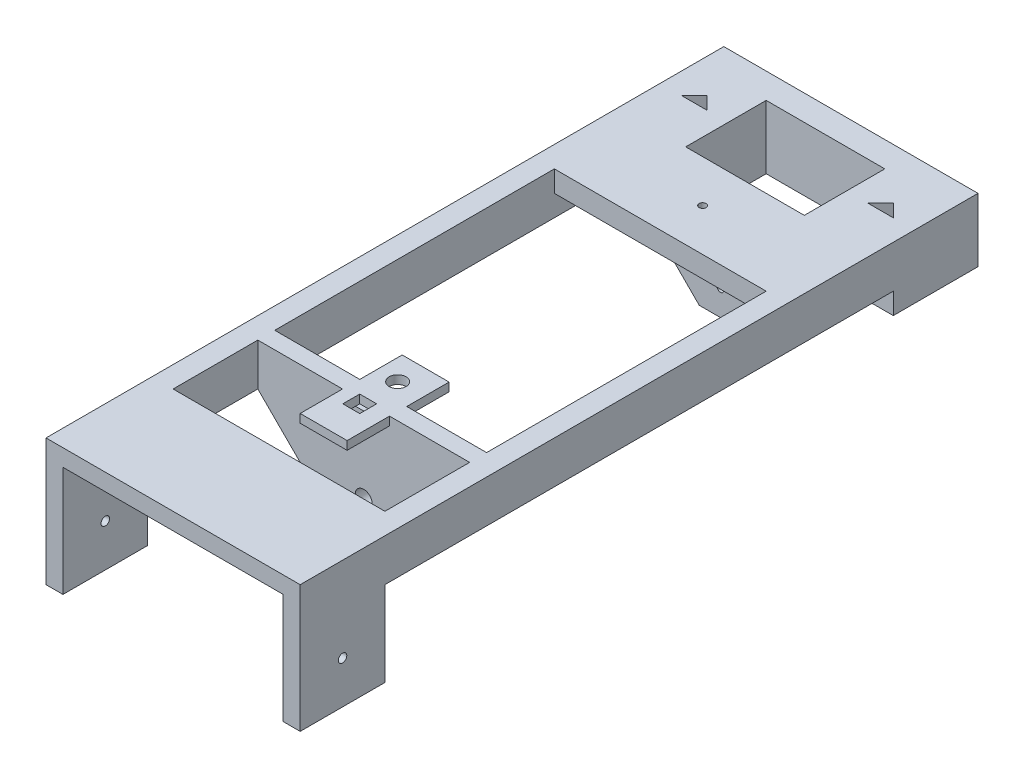
SolidWorks part; units mm, degrees
other "Markup1"
sketch "Sketch19" plane through (-15, 15, -40) normal (-0.0389, 0.0826, -0.9958) x (-0.519, -0.8533, -0.0505)
material "Alumina"
ref_plane "Front Plane" through (0, 0, 0) normal (0, 0, 1) x (1, 0, 0)
ref_plane "Top Plane" through (0, 0, 0) normal (0, 1, 0) x (1, 0, 0)
ref_plane "Right Plane" through (0, 0, 0) normal (1, 0, 0) x (0, 0, -1)
sketch "Sketch1" plane through (0, 0, 0) normal (0, 1, 0) x (1, 0, 0)
  line L1 (-15, 40) -> (15, 40)
  line L2 (-15, 40) -> (-15, -40)
  line L3 (-15, -40) -> (15, -40)
  line L4 (15, 40) -> (15, -40)
  line L5 (-15, 40) -> (15, -40) construction
  line L6 (-15, -40) -> (15, 40) construction
  point P0 (0, 0)
  dimension "D1" = 30
  dimension "D2" = 80
extrude "Boss-Extrude1" add sketch "Sketch1" along normal blind 5
sketch "Sketch2" plane through (15, 0, 0) normal (1, 0, 0) x (0, 0, -1)
  line L1 (-40, 0) -> (-30, 0)
  line L2 (-40, 0) -> (-40, -10)
  line L3 (-40, -10) -> (-30, -10)
  line L4 (-30, 0) -> (-30, -10)
  line L5 (40, 0) -> (30, 0)
  line L6 (40, 0) -> (40, -10)
  line L7 (40, -10) -> (30, -10)
  line L8 (30, 0) -> (30, -10)
  dimension "D1" = 10
  dimension "D2" = 10
  dimension "D3" = 10
  dimension "D4" = 10
extrude "Boss-Extrude2" add sketch "Sketch2" against normal blind 30
sketch "Sketch3" plane through (15, 0, 0) normal (1, 0, 0) x (0, 0, -1)
  line L0 (-40, 5) -> (-40, -10) construction
  line L2 (-40, -10) -> (-30, -10) construction
  line L15 (40, 5) -> (40, -10) construction
  line L16 (30, -10) -> (40, -10)
  line L17 (30, -10) -> (30, -2.5)
  line L18 (30, -2.5) -> (40, -2.5)
  line L19 (40, -10) -> (40, -2.5)
  circle A0 centre (-35, -5) radius 0.5
  dimension "D1" = 1
  dimension "D2" = 7.5
  dimension "D3" = 5
  dimension "D4" = 5
extrude "Cut-Extrude1" cut sketch "Sketch3" against normal through all both and the other way through all
sketch "Sketch4" plane through (0, 5, 0) normal (0, 1, 0) x (1, 0, 0)
  line L9 (-12.5, -27.5) -> (12.5, -27.5)
  line L10 (-12.5, -27.5) -> (-12.5, 27.5)
  line L11 (-12.5, 27.5) -> (12.5, 27.5)
  line L12 (12.5, -27.5) -> (12.5, 27.5)
  line L13 (-12.5, -27.5) -> (12.5, 27.5) construction
  line L14 (-12.5, 27.5) -> (12.5, -27.5) construction
  point P0 (0, 0)
  dimension "D1" = 55
  dimension "D2" = 25
extrude "Cut-Extrude2" cut sketch "Sketch4" against normal through all both and the other way through all
sketch "Sketch20" plane through (0, 5, 0) normal (0, 1, 0) x (1, 0, 0)
  line L0 (11, 34) -> (9.5, 32.5)
  line L1 (11, 34) -> (12.5, 32.5)
  line L2 (9.5, 32.5) -> (12.5, 32.5)
  line L3 (-11, 34) -> (-12.5, 32.5)
  line L4 (-11, 34) -> (-9.5, 32.5)
  line L5 (-12.5, 32.5) -> (-9.5, 32.5)
  line L6 (-15, 40) -> (-15, -40) construction
  line L7 (15, -40) -> (15, 40) construction
  line L9 (12.5, 27.5) -> (-12.5, 27.5) construction
  dimension "D1" = 3
  dimension "D2" = 3
  dimension "D3" = 5
  dimension "D4" = 5
  dimension "D5" = 2.5
  dimension "D6" = 2.5
extrude "Cut-Extrude4" cut sketch "Sketch20" against normal through all both and the other way through all
sketch "Sketch22" plane through (0, 0, 40) normal (0, 0, 1) x (1, 0, 0)
  line L0 (-15, -10) -> (15, -10) construction
  line L1 (-13, -10) -> (13, -10)
  line L2 (-13, -10) -> (-13, 3)
  line L3 (-13, 3) -> (13, 3)
  line L4 (13, -10) -> (13, 3)
  line L5 (-15, 5) -> (15, 5) construction
  line L6 (-15, 5) -> (-15, -10) construction
  line L7 (15, 5) -> (15, -10) construction
  dimension "D1" = 2
  dimension "D2" = 2
  dimension "D3" = 2
extrude "Cut-Extrude6" cut sketch "Sketch22" against normal up to surface (10 mm away) up to face at (0, -5, 30)
sketch "Sketch23" plane through (0, 5, 0) normal (0, 1, 0) x (1, 0, 0)
  line L0 (-12.5, 27.5) -> (-12.5, -27.5) construction
  line L5 (12.5, -27.5) -> (12.5, 27.5) construction
  line L7 (-12.5, -17.5) -> (12.5, -17.5)
  line L8 (-12.5, -17.5) -> (-12.5, -15.5)
  line L9 (-12.5, -15.5) -> (12.5, -15.5)
  line L10 (12.5, -17.5) -> (12.5, -15.5)
  line L11 (-12.5, -27.5) -> (12.5, -27.5) construction
  dimension "D1" = 2
  dimension "D4" = 10
extrude "Boss-Extrude3" add sketch "Sketch23" against normal blind 15
sketch "Sketch24" plane through (0, 0, 17.5) normal (0, 0, 1) x (1, 0, 0)
  line L0 (-12.5, -10) -> (12.5, -10) construction
  line L1 (-12.5, -10) -> (-12.5, 0) construction
  circle A0 centre (0, -5) radius 1
  dimension "D1" = 2
  dimension "D2" = 5
  dimension "D3" = 12.5
extrude "Cut-Extrude7" cut sketch "Sketch24" against normal up to surface (2 mm away) contours A0 up to face at (0, -1.6667, 15.5)
chamfer "Chamfer1" distance 10 angle 45 2 edges at (-12.5, -10, 16.5) (12.5, -10, 16.5)
sketch "Sketch25" plane through (0, 5, 0) normal (0, 1, 0) x (1, 0, 0)
  line L0 (3.0765, -15.5) -> (-2.4635, -15.5)
  line L7 (-2.4635, -15.5) -> (-2.4635, -10.5)
  line L8 (-2.4635, -10.5) -> (3.0765, -10.5)
  line L9 (3.0765, -15.5) -> (3.0765, -10.5)
  line L10 (-2.4635, -15.5) -> (3.0765, -10.5) construction
  line L11 (-2.4635, -10.5) -> (3.0765, -15.5) construction
  line L12 (-2.5, -17.5) -> (3.04, -17.5)
  line L13 (-2.5, -17.5) -> (-2.5, -22.5)
  line L14 (-2.5, -22.5) -> (3.04, -22.5)
  line L15 (3.04, -17.5) -> (3.04, -22.5)
  point P0 (0, 0)
  point P1 (0.3065, -13)
  dimension "D1" = 5
  dimension "D2" = 5.54
  dimension "D3" = 5.54
  dimension "D4" = 5
extrude "Boss-Extrude4" add sketch "Sketch25" against normal blind 1
sketch "Sketch26" plane through (0, 5, 0) normal (0, 1, 0) x (1, 0, 0)
  line L1 (-2.4635, -15.5) -> (-12.5, -15.5) construction
  circle A0 centre (0, -13.5) radius 1
  dimension "D1" = 2
  dimension "D2" = 2
extrude "Cut-Extrude8" cut sketch "Sketch26" against normal through all both and the other way through all
sketch "Sketch27" plane through (0, 5, 0) normal (0, 1, 0) x (1, 0, 0)
  line L1 (-0.9711, -19) -> (1.0289, -19)
  line L2 (-0.9711, -19) -> (-0.9711, -17)
  line L3 (-0.9711, -17) -> (1.0289, -17)
  line L4 (1.0289, -19) -> (1.0289, -17)
  line L5 (-0.9711, -19) -> (1.0289, -17) construction
  line L6 (-0.9711, -17) -> (1.0289, -19) construction
  circle A0 centre (0, -13.5) radius 1 construction
  point P0 (0.0289, -18)
  dimension "D3" = 4.5
  dimension "D1" = 2
  dimension "D2" = 2
extrude "Cut-Extrude9" cut sketch "Sketch27" against normal blind 1
sketch "Sketch28" plane through (0, 5, 0) normal (0, 1, 0) x (1, 0, 0)
  line L2 (12.5, 27.5) -> (-12.5, 27.5) construction
  line L3 (-7, 27.5) -> (7, 27.5)
  line L4 (-7, 27.5) -> (-7, 37)
  line L5 (-7, 37) -> (7, 37)
  line L6 (7, 27.5) -> (7, 37)
  line L7 (-15, 40) -> (-15, -40) construction
  line L8 (15, -40) -> (15, 40) construction
  line L9 (15, 40) -> (-15, 40) construction
  dimension "D1" = 8
  dimension "D2" = 8
  dimension "D3" = 3
extrude "Cut-Extrude11" cut sketch "Sketch28" against normal through all both and the other way through all
sketch "Sketch29" plane through (0, 5, 0) normal (0, 1, 0) x (1, 0, 0)
  line L0 (-12.5, 27.5) -> (-12.5, -15.5) construction
  line L1 (-12.5, 17.5) -> (12.5, 17.5)
  line L2 (-12.5, 17.5) -> (-12.5, 27.5)
  line L3 (-12.5, 27.5) -> (12.5, 27.5)
  line L4 (12.5, 17.5) -> (12.5, 27.5)
  line L5 (12.5, -15.5) -> (12.5, 27.5) construction
  line L6 (-7, 27.5) -> (-12.5, 27.5) construction
  dimension "D1" = 10
  dimension "D2" = 0
extrude "Boss-Extrude5" add sketch "Sketch29" against normal blind 2.5
sketch "Sketch30" plane through (0, 5, 0) normal (0, 1, 0) x (1, 0, 0)
  line L0 (-12.5, 17.5) -> (12.5, 17.5) construction
  circle A0 centre (0, 22.5) radius 0.415
  dimension "D1" = 0.83
  dimension "D2" = 5
extrude "Cut-Extrude12" cut sketch "Sketch30" against normal through all both and the other way through all
sketch "Sketch31" plane through (0, 2.5, 0) normal (0, -1, 0) x (1, 0, 0)
  line L0 (12.5, -17.5) -> (12.5, -27.5) construction
  line L1 (-12.5, -27.5) -> (12.5, -27.5)
  line L2 (-12.5, -27.5) -> (-12.5, -24.6017)
  line L3 (-12.5, -24.6017) -> (12.5, -24.6017)
  line L4 (12.5, -27.5) -> (12.5, -24.6017)
extrude "Boss-Extrude6" add sketch "Sketch31" along normal blind 10
sketch "Sketch32" plane through (0, 0, -27.5) normal (0, 0, -1) x (-1, 0, 0)
  line L0 (12.5, -7.5) -> (-12.5, -7.5) construction
  circle A0 centre (0, -4.52) radius 0.4
  dimension "D2" = 0.8
  dimension "D1" = 2.98
extrude "Cut-Extrude13" cut sketch "Sketch32" against normal up to surface (2.8983 mm away) up to face at (0, -1.6667, -24.6017)
chamfer "Chamfer2" distance 10 angle 45 2 edges at (12.5, -7.5, -26.0508) (-12.5, -7.5, -26.0508)
scale "Scale1" scale about centroid uniform scaling yes scale factor 6
equation "\"w\"=3.9113"
